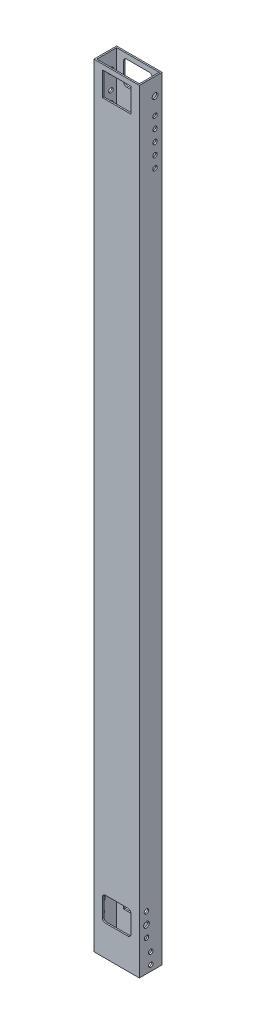
SolidWorks part; units mm, degrees
material "6061-T6 (SS)"
ref_plane "Front Plane" through (0, 0, 0) normal (0, 0, 1) x (1, 0, 0)
ref_plane "Top Plane" through (0, 0, 0) normal (0, 1, 0) x (1, 0, 0)
ref_plane "Right Plane" through (0, 0, 0) normal (1, 0, 0) x (0, 0, -1)
sketch "Sketch1" plane through (0, 0, 0) normal (0, 0, 1) x (1, 0, 0)
  line L1 (-25.4, -431.8) -> (25.4, -431.8)
  line L2 (-25.4, -431.8) -> (-25.4, 431.8)
  line L3 (-25.4, 431.8) -> (25.4, 431.8)
  line L4 (25.4, -431.8) -> (25.4, 431.8)
  line L5 (-25.4, -431.8) -> (25.4, 431.8) construction
  line L6 (-25.4, 431.8) -> (25.4, -431.8) construction
  point P0 (0, 0)
  dimension "D1" = 50.8
  dimension "D2" = 863.6
extrude "Boss-Extrude1" add sketch "Sketch1" along normal mid plane 25.4
shell "Shell1" thickness 1.5875 removed face at (0, -431.8, 0) removed face at (0, 431.8, 0)
sketch "Sketch3" plane through (0, 0, 0) normal (1, 0, 0) x (0, 0, -1)
  line L0 (-12.7, -431.8) -> (12.7, -431.8) construction
  circle A0 centre (0, -425.45) radius 2.4892
  circle A1 centre (0, -412.75) radius 2.4892
  point P6 (0, -431.8)
  dimension "D1" = 4.9784
  dimension "D2" = 6.35
  dimension "D3" = 12.7
extrude "Cut-Extrude1" cut sketch "Sketch3" against normal through all both and the other way through all
sketch "Sketch4" plane through (0, 0, 0) normal (1, 0, 0) x (0, 0, -1)
  line L4 (-12.7, -431.8) -> (12.7, -431.8) construction
  line L5 (-12.7, 431.8) -> (-12.7, -431.8) construction
  circle A3 centre (-4.7625, -384.175) radius 3.175
  circle A4 centre (-4.7625, -371.475) radius 2.4892
  circle A5 centre (-4.7625, -396.875) radius 2.4892
  dimension "D7" = 6.35
  dimension "D8" = 4.9784
  dimension "D9" = 12.7
  dimension "D10" = 12.7
  dimension "D11" = 47.625
  dimension "D12" = 7.9375
extrude "Cut-Extrude2" cut sketch "Sketch4" against normal through all both and the other way through all
sketch "Sketch5" plane through (0, 0, 0) normal (0, 0, 1) x (1, 0, 0)
  line L0 (-25.4, -431.8) -> (25.4, -431.8) construction
  line L1 (-15.875, -370.6813) -> (15.875, -370.6813)
  line L2 (-15.875, -370.6813) -> (-15.875, -397.6688)
  line L3 (-15.875, -397.6688) -> (15.875, -397.6688)
  line L4 (15.875, -370.6813) -> (15.875, -397.6688)
  point P4 (0, -397.6688)
  point P7 (0, -431.8)
  point P8 (15.875, -384.175)
  dimension "D1" = 31.75
  dimension "D2" = 26.9875
  dimension "D3" = 47.625
extrude "Cut-Extrude3" cut sketch "Sketch5" along normal through all both and the other way through all
fillet "Fillet1" radius 3.175 4 edges at (-15.875, -397.6688, 11.9062) (15.875, -397.6688, 11.9062) (-15.875, -370.6813, 11.9062) (15.875, -370.6813, 11.9062)
sketch "Sketch6" plane through (0, 0, 0) normal (1, 0, 0) x (0, 0, -1)
  line L0 (12.7, 431.8) -> (12.7, -431.8) construction
  line L1 (-12.7, 431.8) -> (12.7, 431.8) construction
  circle A0 centre (4.7625, 412.75) radius 3.175
  dimension "D1" = 6.35
  dimension "D2" = 7.9375
  dimension "D3" = 19.05
extrude "Cut-Extrude4" cut sketch "Sketch6" against normal through all both and the other way through all
sketch "Sketch7" plane through (0, 0, 0) normal (0, 0, 1) x (1, 0, 0)
  line L0 (25.4, 431.8) -> (-25.4, 431.8) construction
  line L1 (15.875, 426.2437) -> (-15.875, 426.2437)
  line L2 (15.875, 426.2437) -> (15.875, 399.2562)
  line L3 (15.875, 399.2562) -> (-15.875, 399.2562)
  line L4 (-15.875, 426.2437) -> (-15.875, 399.2562)
  point P5 (0, 426.2437)
  point P8 (0, 431.8)
  point P9 (-15.875, 412.75)
  dimension "D1" = 26.9875
  dimension "D2" = 31.75
  dimension "D3" = 19.05
extrude "Cut-Extrude5" cut sketch "Sketch7" against normal through all both and the other way through all
fillet "Fillet2" radius 3.175 4 edges at (15.875, 399.2562, -11.9062) (-15.875, 399.2562, -11.9062) (-15.875, 426.2437, -11.9062) (15.875, 426.2437, -11.9062)
sketch "Sketch8" plane through (0, 0, 0) normal (1, 0, 0) x (0, 0, -1)
  line L0 (12.7, 431.8) -> (12.7, -431.8) construction
  line L1 (-12.7, 431.8) -> (12.7, 431.8) construction
  circle A0 centre (4.7625, 393.7) radius 2.4892
  circle A1 centre (4.7625, 381) radius 2.4892
  circle A2 centre (4.7625, 368.3) radius 2.4892
  circle A3 centre (4.7625, 355.6) radius 2.4892
  circle A4 centre (4.7625, 342.9) radius 2.4892
  dimension "D3" = 4.9784
  dimension "D1" = 7.9375
  dimension "D2" = 38.1
  dimension "D5" = 12.7
  dimension "D4" = 5
extrude "Cut-Extrude6" cut sketch "Sketch8" against normal through all both and the other way through all
